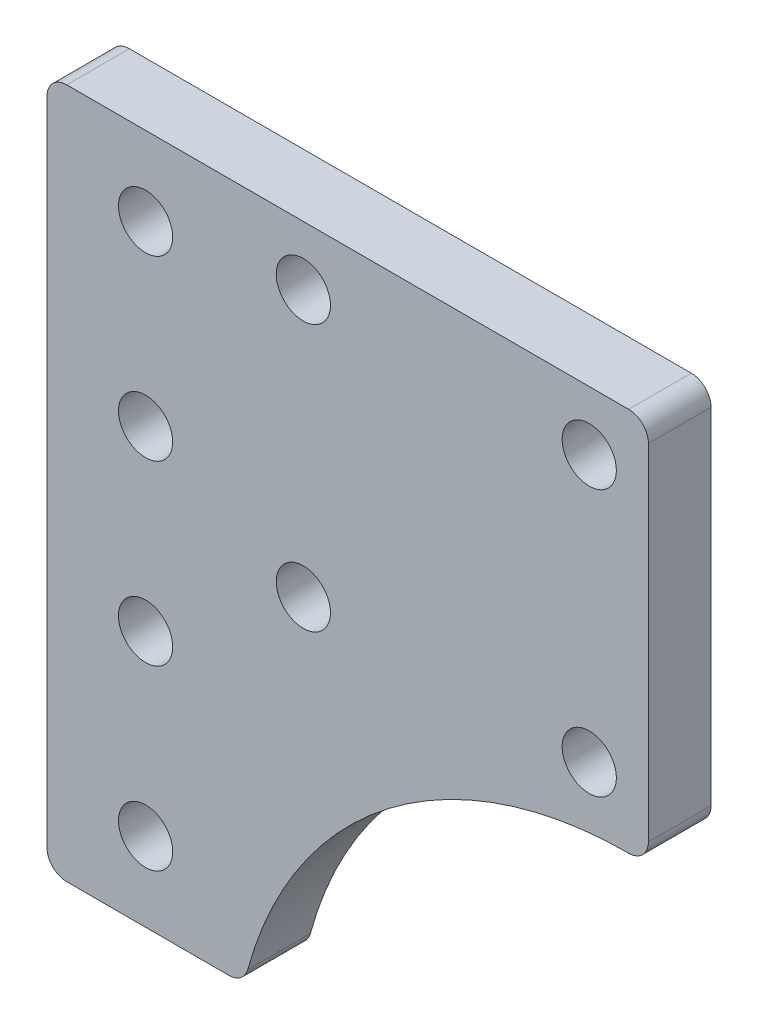
SolidWorks part; units mm, degrees
ref_plane "Front Plane" through (0, 0, 0) normal (0, 0, 1) x (1, 0, 0)
ref_plane "Top Plane" through (0, 0, 0) normal (0, 1, 0) x (1, 0, 0)
ref_plane "Right Plane" through (0, 0, 0) normal (1, 0, 0) x (0, 0, -1)
sketch "Sketch2" plane through (0, 0, 0) normal (0, 0, 1) x (1, 0, 0)
  line L0 (0, 0) -> (20, 0)
  line L5 (20, 0) -> (20, 31)
  line L6 (20, 31) -> (61, 31)
  line L7 (61, 31) -> (61, 70)
  line L8 (61, 70) -> (0, 70)
  line L11 (0, 70) -> (0, 0)
  dimension "D1" = 39
  dimension "D2" = 61
  dimension "D4" = 20
  dimension "D5" = 31
extrude "Boss-Extrude1" add sketch "Sketch2" along normal blind 6.35
sketch "Sketch4" plane through (0, 0, 0) normal (0, 0, -1) x (-1, 0, 0)
  circle A0 centre (-55, 64) radius 2.5 construction
  circle A1 centre (-55, 64) radius 2.5 construction
  circle A2 centre (-55, 37) radius 2.5 construction
  circle A3 centre (-55, 37) radius 2.5 construction
  circle A4 centre (-26, 37) radius 2.5 construction
  circle A5 centre (-26, 37) radius 2.5 construction
  circle A6 centre (-26, 64) radius 2.5 construction
  circle A7 centre (-26, 64) radius 2.5 construction
  circle A8 centre (-26, 64) radius 2.75
  circle A9 centre (-55, 64) radius 2.75
  circle A10 centre (-55, 37) radius 2.75
  circle A11 centre (-26, 37) radius 2.75
  dimension "D1" = 5.5
  dimension "D2" = 5.5
  dimension "D3" = 5.5
  dimension "D4" = 5.5
extrude "Cut-Extrude1" cut sketch "Sketch4" against normal blind 10
sketch "Sketch5" plane through (0, 0, 6.35) normal (0, 0, 1) x (1, 0, 0)
  line L0 (10, 0) -> (10, 70) construction
  line L1 (0, 0) -> (20, 0) construction
  line L2 (61, 70) -> (0, 70) construction
  circle A0 centre (10, 8) radius 2.75
  circle A1 centre (10, 26) radius 2.75
  circle A2 centre (10, 44) radius 2.75
  circle A3 centre (10, 62) radius 2.75
  dimension "D1" = 5.5
  dimension "D2" = 5.5
  dimension "D3" = 5.5
  dimension "D4" = 5.5
  dimension "D6" = 18
  dimension "D7" = 18
  dimension "D8" = 18
  dimension "D5" = 8
  dimension "D9" = 8
extrude "Cut-Extrude2" cut sketch "Sketch5" against normal through all
fillet "Fillet1" radius 40 1 edges at (20, 31, 3.175)
fillet "Fillet2" radius 2 5 edges at (0, 70, 3.175) (61, 70, 3.175) (61, 31, 3.175) (0, 0, 3.175) (20, 0, 3.175)
